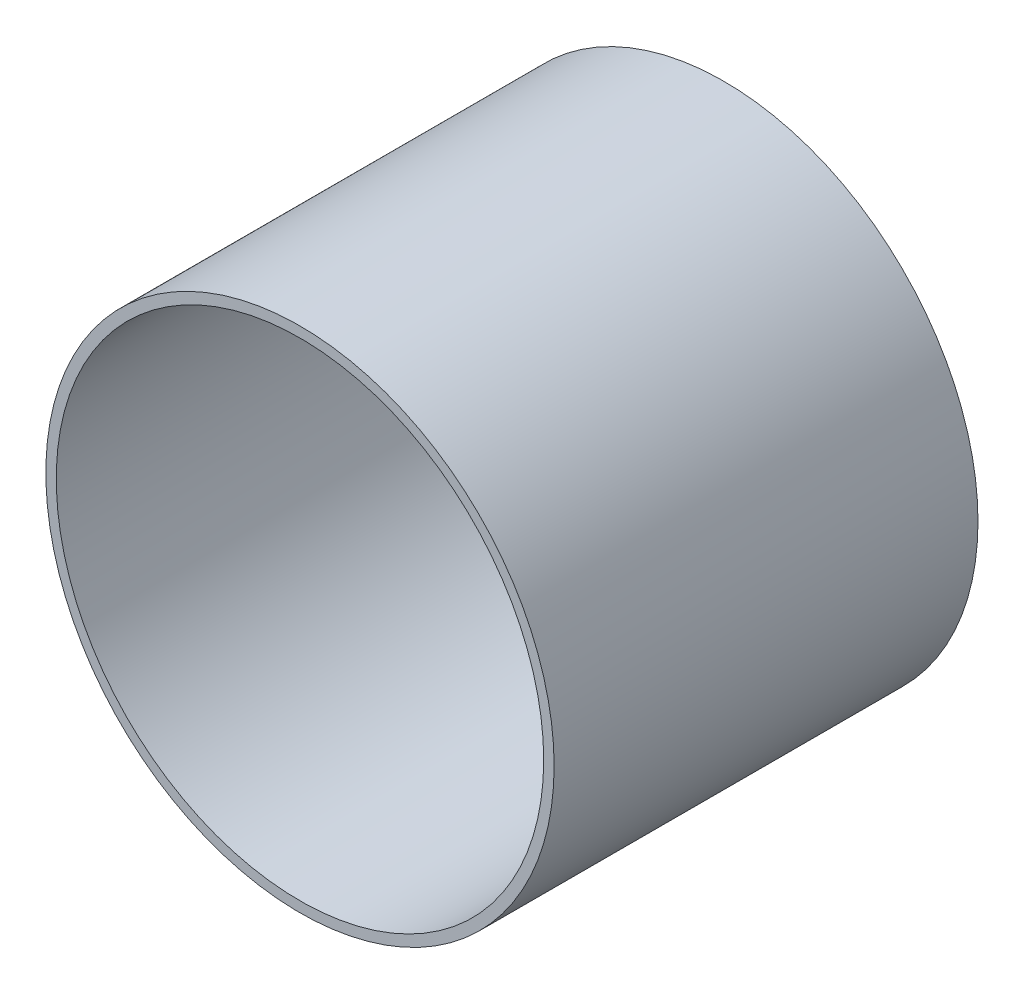
SolidWorks part; units mm, degrees
ref_plane "Front Plane" through (0, 0, 0) normal (0, 0, 1) x (1, 0, 0)
ref_plane "Top Plane" through (0, 0, 0) normal (0, 1, 0) x (1, 0, 0)
ref_plane "Right Plane" through (0, 0, 0) normal (1, 0, 0) x (0, 0, -1)
sketch "Sketch1" plane through (0, 0, 0) normal (0, 0, 1) x (1, 0, 0)
  circle A0 centre (0, 0) radius 38.0746
  circle A1 centre (0, 0) radius 36.5125
  dimension "D1" = 73.025
  dimension "D2" = 76.1492
extrude "Boss-Extrude1" add sketch "Sketch1" along normal mid plane 63.5
equation "\"AIRFRAME_OD\"= 3.091in"
equation "\"AIRFRAME_ID\"= 3.00in"
equation "\"FLAT_T\" = 0.125in"
equation "\"NOSE_EXP_L\"= 3.5in"
equation "\"NOSE_SHOULDER_L\" = 5in"
equation "\"MAIN_L\" = 30in"
equation "\"RECO_COUP_L\" = 6in"
equation "\"RECO_SWITCH_L\" = 1.5in"
equation "\"DROGUE_L\" = 14in"
equation "\"ATS_FORE_COUP_L\" = 4in"
equation "\"ATS_AFT_COUP_L\" = 2.5in"
equation "\"LOWER_L\" = 16in"
equation "\"FIN_N\" = 4"
equation "\"CR_AFT_X\" = 0.5in"
equation "\"CR_FORE_X\" = 6in"
equation "\"D1@Sketch1\"=\"COUPLER_ID\""
equation "\"D2@Sketch1\"=\"COUPLER_OD\""
equation "\"D1@Boss-Extrude1\"=\"ATS_AFT_COUP_L\""
equation "\"FIN_ROOT\" = 5in"
equation "\"FIN_X\" = 0.75in"
equation "\"MOTOR_OD\" = 2.25in"
equation "\"MOTOR_ID\" = 2.126in"
equation "\"COUPLER_OD\" = 2.998in"
equation "\"COUPLER_ID\" = 2.875in"
equation "\"RECO_ROD_X\" = 1.5in"
equation "\"ATS_ROD_X\" = 2in"
equation "\"MOTOR_L\" = 8in"
equation "\"MOTOR_LOWER_X\" = 0.5in"
